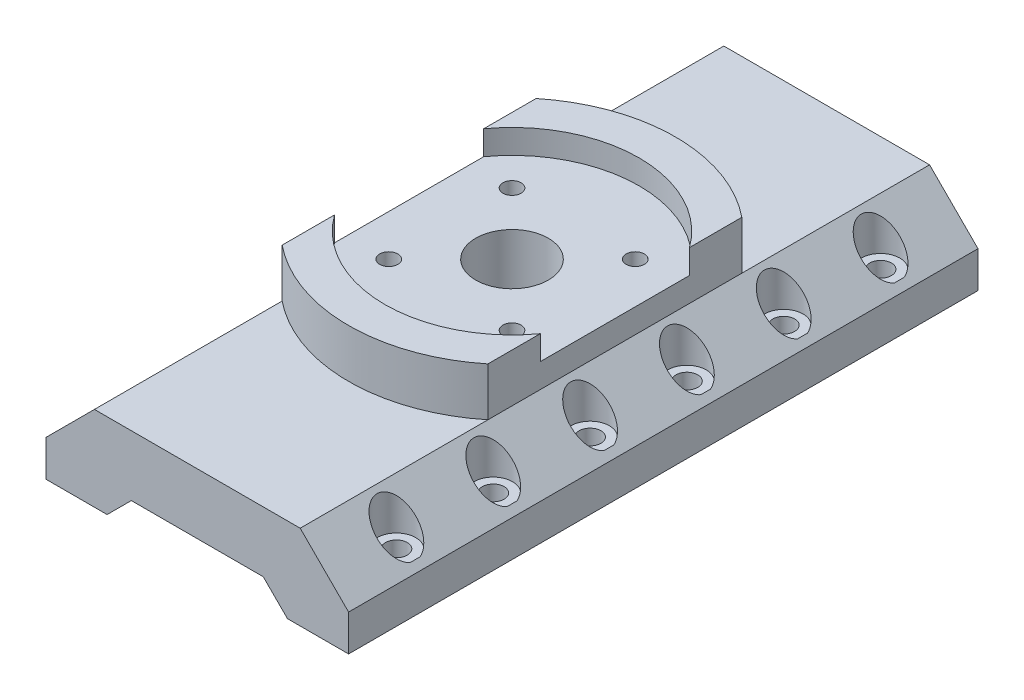
SolidWorks part; units mm, degrees
note: The reader was unsure of these and kept them because the rebuilt part matched: shared geometry of "Sketch12<3>".
ref_plane "Front Plane" through (0, 0, 0) normal (0, 0, 1) x (1, 0, 0)
ref_plane "Top Plane" through (0, 0, 0) normal (0, 1, 0) x (1, 0, 0)
ref_plane "Right Plane" through (0, 0, 0) normal (1, 0, 0) x (0, 0, -1)
sketch "Sketch1" plane through (0, 0, 0) normal (0, 1, 0) x (1, 0, 0)
  line L1 (-12.5, -26) -> (12.5, -26)
  line L2 (-12.5, -26) -> (-12.5, 26)
  line L3 (-12.5, 26) -> (12.5, 26)
  line L4 (12.5, -26) -> (12.5, 26)
  line L5 (-12.5, -26) -> (12.5, 26) construction
  line L6 (-12.5, 26) -> (12.5, -26) construction
  point P0 (0, 0)
  dimension "D1" = 25
  dimension "D2" = 52
extrude "Boss-Extrude1" add sketch "Sketch1" along normal blind 7
sketch "Sketch2" plane through (0, 7, 0) normal (0, 1, 0) x (1, 0, 0)
  line L0 (-10.45, -20) -> (10.45, -20) construction
  line L1 (-12.5, -26) -> (12.5, -26) construction
  circle A0 centre (-10.45, -20) radius 0.9
  circle A1 centre (10.45, -20) radius 0.9
  point P4 (0, -20)
  dimension "D1" = 1.8
  dimension "D2" = 20.9
  dimension "D3" = 6
extrude "Cut-Extrude1" cut sketch "Sketch2" against normal through all
pattern_linear "LPattern1" count 6 spacing 8 along (0, 0, -1) of "Cut-Extrude1"
sketch "Sketch9" plane through (0, 7, 0) normal (0, 1, 0) x (1, 0, 0)
  circle A0 centre (-10.45, 20) radius 1.875
  circle A2 centre (10.45, 20) radius 1.6
  dimension "D1" = 3.75
  dimension "D2" = 3.2
extrude "Cut-Extrude3" cut sketch "Sketch9" against normal blind 3.5
pattern_linear "LPattern2" count 6 spacing 8 along (0, 0, 1) of "Cut-Extrude3"
chamfer "Chamfer2" distance 4 angle 45 2 edges at (-12.5, 7, 0) (12.5, 7, 0)
sketch "Sketch10" plane through (0, 0, 0) normal (0, -1, 0) x (1, 0, 0)
  line L0 (12.5, -26) -> (-12.5, -26) construction
  line L1 (-7.45, -26) -> (7.45, -26)
  line L2 (-7.45, -26) -> (-7.45, 26)
  line L3 (-7.45, 26) -> (7.45, 26)
  line L4 (7.45, -26) -> (7.45, 26)
  line L5 (-12.5, 26) -> (12.5, 26) construction
  circle A0 centre (10.45, 20) radius 0.9 construction
  circle A1 centre (-10.45, 20) radius 0.9 construction
  dimension "D1" = 3
  dimension "D2" = 3
extrude "Cut-Extrude4" cut sketch "Sketch10" against normal blind 2
chamfer "Chamfer3" distance 2 angle 45 2 edges at (7.45, 2, 0) (-7.45, 2, 0)
sketch "Sketch12" plane through (0, 7, 0) normal (0, 1, 0) x (1, 0, 0)
  line L0 (-8.5, 26) -> (-8.5, -26) construction
  line L1 (-8.5, 26) -> (-8.5, -26)
  line L2 (8.5, -26) -> (8.5, 26) construction
  line L3 (8.5, -26) -> (8.5, 26)
  circle A0 centre (0, 0) radius 10.5
  circle A1 centre (0, 0) radius 13.5
  line M3 (-8.5, 26) -> (-8.5, -26)
  line M5 (8.5, -26) -> (8.5, 26)
  dimension "D1" = 21
  dimension "D2" = 3
extrude "Boss-Extrude2" add sketch "Sketch12" along normal blind 2 contours A1 L1 A0 M5 | L1 A1 A0 M3 | A1 L3 A0 M3 | L3 A1 A0 M5 | L1 A0 | L3 A0
extrude "Boss-Extrude3" add sketch "Sketch12<3>" along normal blind 4 contours A1 L1 A0 M5 | A1 L3 A0 M3
sketch "Sketch12<3>" plane through (0, 7, 0) normal (0, 1, 0) x (1, 0, 0) same geometry as "Sketch12"
sketch "Sketch13" plane through (0, 9, 0) normal (0, 1, 0) x (1, 0, 0)
  line L0 (-5.0912, 5.0912) -> (0, 0) construction
  line L1 (0, 0) -> (-7.2, 0) construction
  circle A0 centre (0, 0) radius 7.2 construction
  circle A1 centre (-5.0912, 5.0912) radius 0.75
  circle A2 centre (5.0912, 5.0912) radius 0.75
  circle A3 centre (5.0912, -5.0912) radius 0.75
  circle A4 centre (-5.0912, -5.0912) radius 0.75
  point P15 (0, 0)
  dimension "D2" = 1.5
  dimension "D3" = 14.4
  dimension "D1" = 45
  dimension "D4" = 4
extrude "Cut-Extrude5" cut sketch "Sketch13" against normal blind 3
sketch "Sketch14" plane through (0, 6, 0) normal (0, 1, 0) x (1, 0, 0)
  circle A0 centre (-5.0912, 5.0912) radius 1.75
  circle A1 centre (5.0912, 5.0912) radius 1.75
  circle A2 centre (5.0912, -5.0912) radius 1.75
  circle A3 centre (-5.0912, -5.0912) radius 1.75
  point P12 (0, 0)
  dimension "D1" = 3.5
  dimension "D2" = 4
extrude "Cut-Extrude6" cut sketch "Sketch14" against normal up to next
sketch "Sketch15" plane through (0, 9, 0) normal (0, 1, 0) x (1, 0, 0)
  circle A0 centre (0, 0) radius 3
  dimension "D1" = 6
extrude "Cut-Extrude7" cut sketch "Sketch15" against normal up to next
